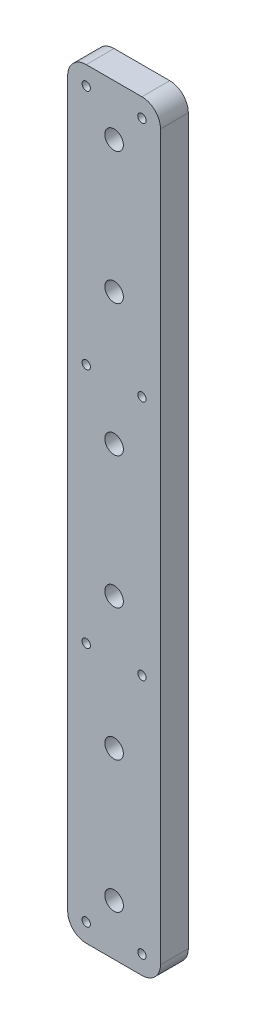
SolidWorks part; units mm, degrees
ref_plane "Front" through (0, 0, 0) normal (0, 0, 1) x (1, 0, 0)
ref_plane "Top" through (0, 0, 0) normal (0, 1, 0) x (1, 0, 0)
ref_plane "Right" through (0, 0, 0) normal (1, 0, 0) x (0, 0, -1)
sketch "Esquisse1" plane through (0, 0, 0) normal (0, 0, 1) x (1, 0, 0)
  line L1 (0, 0) -> (50, 0)
  line L2 (0, 0) -> (0, 410)
  line L3 (0, 410) -> (50, 410)
  line L4 (50, 0) -> (50, 410)
  dimension "D1" = 50
  dimension "D2" = 410
extrude "Boss.-Extru.1" add sketch "Esquisse1" along normal blind 15
sketch "Esquisse2" plane through (0, 0, 15) normal (0, 0, 1) x (1, 0, 0)
  line L0 (50, 205) -> (0, 205) construction
  line L1 (50, 0) -> (50, 410) construction
  line L2 (0, 410) -> (0, 0) construction
  line L3 (25, 240.5) -> (25, 205) construction
  line L4 (25, 240.5) -> (25, 311.5) construction
  line L5 (25, 311.5) -> (25, 382.5) construction
  line L6 (25, 98.5) -> (25, 27.5) construction
  line L7 (25, 169.5) -> (25, 98.5) construction
  line L8 (40, 205) -> (40, 270) construction
  line L9 (40, 270) -> (40, 400) construction
  line L10 (40, 140) -> (40, 10) construction
  line L11 (10, 140) -> (10, 10) construction
  line L12 (10, 270) -> (10, 400) construction
  line L13 (10, 205) -> (10, 270) construction
  circle A0 centre (25, 240.5) radius 5
  circle A1 centre (25, 311.5) radius 5
  circle A2 centre (25, 382.5) radius 5
  circle A3 centre (25, 27.5) radius 5
  circle A4 centre (25, 98.5) radius 5
  circle A5 centre (25, 169.5) radius 5
  circle A6 centre (40, 270) radius 2.25
  circle A7 centre (40, 400) radius 2.25
  circle A8 centre (40, 10) radius 2.25
  circle A9 centre (40, 140) radius 2.25
  circle A10 centre (10, 140) radius 2.25
  circle A11 centre (10, 10) radius 2.25
  circle A12 centre (10, 400) radius 2.25
  circle A13 centre (10, 270) radius 2.25
  dimension "D1" = 10
  dimension "D2" = 71
  dimension "D3" = 71
  dimension "D4" = 71
  dimension "D7" = 4.5
  dimension "D5" = 65
  dimension "D6" = 15
  dimension "D8" = 130
extrude "Enlèv. mat.-Extru.1" cut sketch "Esquisse2" against normal through all both and the other way through all
fillet "Congé1" radius 10 4 edges at (50, 0, 7.5) (0, 0, 7.5) (50, 410, 7.5) (0, 410, 7.5)
